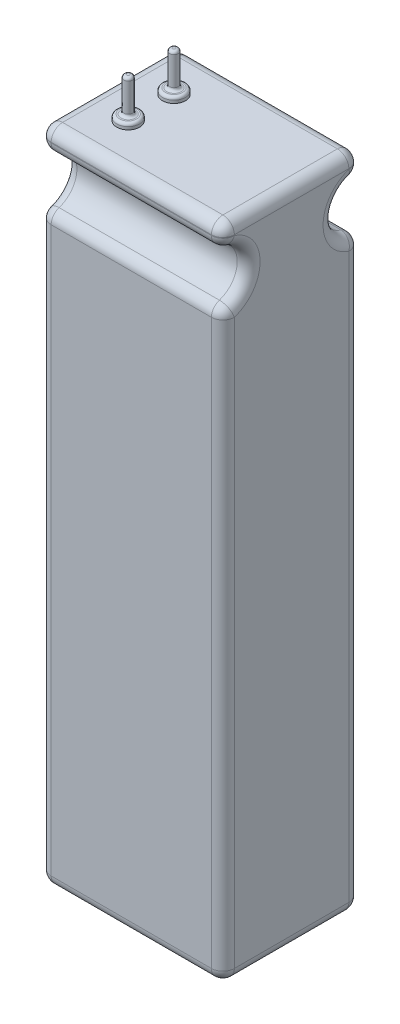
SolidWorks part; units mm, degrees
ref_plane "Front Plane" through (0, 0, 0) normal (0, 0, 1) x (1, 0, 0)
ref_plane "Top Plane" through (0, 0, 0) normal (0, 1, 0) x (1, 0, 0)
ref_plane "Right Plane" through (0, 0, 0) normal (1, 0, 0) x (0, 0, -1)
sketch "Sketch1" plane through (0, 0, 0) normal (0, 1, 0) x (1, 0, 0)
  line L1 (-16, -12) -> (16, -12)
  line L2 (-16, -12) -> (-16, 12)
  line L3 (-16, 12) -> (16, 12)
  line L4 (16, -12) -> (16, 12)
  line L5 (-16, -12) -> (16, 12) construction
  line L6 (-16, 12) -> (16, -12) construction
  point P0 (0, 0)
  dimension "D1" = 24
  dimension "D2" = 32
extrude "Boss-Extrude1" add sketch "Sketch1" along normal blind 115
sketch "Sketch2" plane through (-16, 0, 0) normal (-1, 0, 0) x (0, 0, 1)
  line L0 (12, 115) -> (12, 0) construction
  line L1 (-12, 115) -> (-12, 0) construction
  circle A0 centre (12, 106.6968) radius 4.5
  circle A1 centre (-12, 106.6968) radius 4.5
extrude "Cut-Extrude1" cut sketch "Sketch2" against normal blind 40
fillet "Fillet1" radius 2 2 edges at (0, 111.1968, 12) (0, 102.1968, 12)
fillet "Fillet2" radius 2 5 edges at (-16, 113.9407, 12) (-16, 111.7048, 11.6172) (-16, 50.2561, 12) (-16, 101.6889, 11.6172) (-16, 106.6968, 7.5)
fillet "Fillet3" radius 2 5 edges at (-16, 113.0984, -12) (-16, 106.6968, -7.5) (-16, 51.0984, -12) (0, 111.1968, -12) (0, 102.1968, -12)
fillet "Fillet4" radius 2 10 edges at (16, 50.2561, -12) (16, 101.6889, -11.6172) (16, 113.9407, -12) (16, 111.7048, -11.6172) (16, 113.9407, 12) (16, 111.7048, 11.6172) (16, 50.2561, 12) (16, 101.6889, 11.6172) (16, 106.6968, -7.5) (16, 106.6968, 7.5)
fillet "Fillet5" radius 2 8 edges at (-15.4142, 0, -11.4142) (-16, 0, 0) (-15.4142, 0, 11.4142) (0, 0, 12) (15.4142, 0, 11.4142) (16, 0, 0) (15.4142, 0, -11.4142) (0, 0, -12)
fillet "Fillet6" radius 2 8 edges at (15.4142, 115, 11.4142) (0, 115, 12) (-15.4142, 115, 11.4142) (-16, 115, 0) (-15.4142, 115, -11.4142) (0, 115, -12) (15.4142, 115, -11.4142) (16, 115, 0)
sketch "Sketch3" plane through (0, 115, 0) normal (0, 1, 0) x (1, 0, 0)
  circle A0 centre (-8.5417, -4) radius 2
  circle A1 centre (-8.5417, 4) radius 2
  dimension "D1" = 8
  dimension "D2" = 4
extrude "Boss-Extrude2" add sketch "Sketch3" along normal blind 1
sketch "Sketch4" plane through (0, 115, 0) normal (0, 1, 0) x (1, 0, 0)
  circle A0 centre (-8.5417, -4) radius 0.75
  circle A1 centre (-8.5417, 4) radius 0.75
extrude "Boss-Extrude3" add sketch "Sketch4" along normal blind 7
fillet "Fillet7" radius 0.5 2 edges at (-8.5417, 116, 6) (-8.5417, 116, -2)
fillet "Fillet8" radius 0.5 4 edges at (-8.5417, 122, -3.25) (-8.5417, 122, 4.75) (-8.5417, 116, 4.75) (-8.5417, 116, -3.25)
